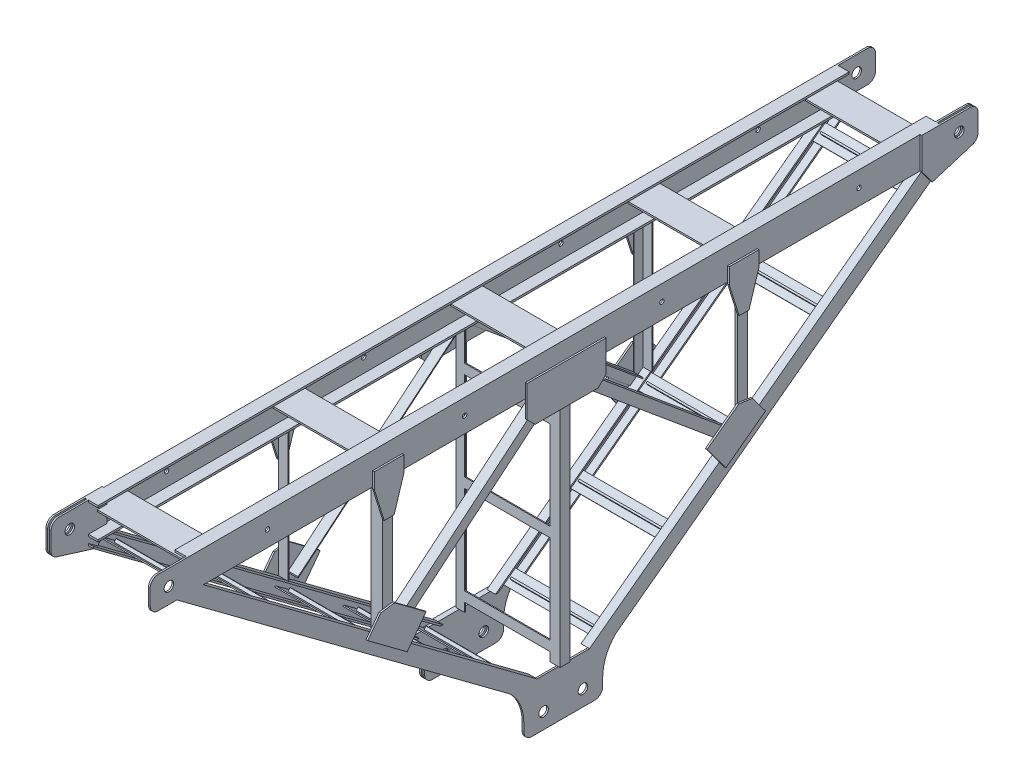
SolidWorks part; units mm, degrees
ref_plane "前视基准面" through (0, 0, 0) normal (0, 0, 1) x (1, 0, 0)
ref_plane "上视基准面" through (0, 0, 0) normal (0, 1, 0) x (1, 0, 0)
ref_plane "右视基准面" through (0, 0, 0) normal (1, 0, 0) x (0, 0, -1)
sketch "草图2" plane through (0, 0, 0) normal (0, 0, 1) x (1, 0, 0)
  line L0 (0, 0) -> (0, 160)
  line L1 (0, 160) -> (65, 160)
  line L2 (65, 160) -> (65, 150)
  line L3 (65, 150) -> (8.5, 150)
  line L4 (8.5, 150) -> (8.5, 10)
  line L5 (8.5, 10) -> (65, 10)
  line L6 (65, 10) -> (65, 0)
  line L7 (65, 0) -> (0, 0)
  line L8 (455, 160) -> (520, 160)
  line L9 (520, 160) -> (520, 0)
  line L10 (520, 0) -> (455, 0)
  line L11 (455, 0) -> (455, 10)
  line L12 (455, 10) -> (511.5, 10)
  line L13 (511.5, 10) -> (511.5, 150)
  line L14 (511.5, 150) -> (455, 150)
  line L15 (455, 150) -> (455, 160)
  dimension "D1" = 160
  dimension "D2" = 10
  dimension "D3" = 8.5
  dimension "D4" = 65
  dimension "D5" = 520
extrude "拉伸1" add sketch "草图2" along normal blind 4190
sketch "草图7" plane through (520, 0, 0) normal (1, 0, 0) x (0, 0, -1)
  line L1 (-2295, -1260) -> (-1895, -1260)
  line L2 (-2295, -1260) -> (-2295, -1500)
  line L3 (-2295, -1500) -> (-1895, -1500)
  line L4 (-1895, -1260) -> (-1895, -1500)
  line L5 (-4190, 160) -> (0, 160) construction
  line L6 (-2095, 160) -> (-2095, -1500) construction
  dimension "D1" = 240
  dimension "D2" = 400
  dimension "D4" = 1660
extrude "拉伸4" add sketch "草图7" against normal blind 520 separate body
sketch "草图8" plane through (0, -1260, 0) normal (0, 1, 0) x (1, 0, 0)
  line L0 (0, -2295) -> (520, -2295) construction
  line L1 (511.5, -2295) -> (8.5, -2295)
  line L2 (511.5, -2295) -> (511.5, -1895)
  line L3 (511.5, -1895) -> (8.5, -1895)
  line L4 (8.5, -2295) -> (8.5, -1895)
  line L5 (0, -1895) -> (520, -1895) construction
  line L6 (0, -1895) -> (0, -2295) construction
  line L7 (520, -1895) -> (520, -2295) construction
  dimension "D1" = 8.5
  dimension "D2" = 8.5
extrude "拉伸5" cut sketch "草图8" against normal through all
sketch "草图9" plane through (520, 0, 0) normal (1, 0, 0) x (0, 0, -1)
  line L0 (-2295, -1500) -> (-1895, -1500) construction
  circle A0 centre (-2195, -1420) radius 11
  circle A1 centre (-1995, -1420) radius 11
  point P6 (-2095, -1500)
  dimension "D1" = 22
  dimension "D2" = 80
  dimension "D3" = 80
  dimension "D4" = 200
  dimension "D5" = 100
extrude "拉伸6" cut sketch "草图9" against normal through all
sketch "草图13" plane through (520, 0, 0) normal (1, 0, 0) x (0, 0, -1)
  line L0 (-2295, -1260) -> (-4095, 80) construction
  line L1 (-95, 80) -> (-1895, -1260) construction
  line L2 (-1961.9855, -1260) -> (-1895, -1260)
  line L3 (-1895, -1260) -> (-2295, -1260) construction
  line L4 (-1895, -1260) -> (-1895, -1309.867)
  line L5 (-1895, -1500) -> (-1895, -1260) construction
  line L6 (-1895, -1309.867) -> (-135.4772, 0)
  line L7 (-4190, 0) -> (0, 0) construction
  line L8 (-135.4772, 0) -> (-269.4482, 0)
  line L9 (-269.4482, 0) -> (-1961.9855, -1260)
  line L10 (-2228.0145, -1260) -> (-2295, -1260)
  line L11 (-2295, -1260) -> (-2295, -1309.867)
  line L12 (-2295, -1260) -> (-2295, -1500) construction
  line L13 (-2295, -1309.867) -> (-4054.5228, 0)
  line L14 (-4054.5228, 0) -> (-3920.5518, 0)
  line L15 (-3920.5518, 0) -> (-2228.0145, -1260)
  line L16 (-4190, 160) -> (0, 160) construction
  line L17 (-4190, 0) -> (-4190, 160) construction
  line L18 (0, 0) -> (0, 160) construction
  dimension "D1" = 80
  dimension "D2" = 40
  dimension "D3" = 80
  dimension "D4" = 40
  dimension "D5" = 80
  dimension "D6" = 95
  dimension "D7" = 95
  dimension "D8" = 80
extrude "拉伸8" add sketch "草图13" against normal blind 43 separate body
sketch "草图14" plane through (477, 0, 0) normal (-1, 0, 0) x (0, 0, 1)
  line L0 (3933.9489, 0) -> (4041.1257, 0)
  line L1 (3920.5518, 0) -> (4054.5228, 0) construction
  line L2 (4041.1257, 0) -> (2295, -1299.8936)
  line L3 (2295, -1309.867) -> (2295, -1260) construction
  line L4 (2295, -1299.8936) -> (2295, -1260)
  line L5 (2295, -1260) -> (2241.4116, -1260)
  line L6 (2295, -1260) -> (2228.0145, -1260) construction
  line L7 (2241.4116, -1260) -> (3933.9489, 0)
  line L8 (4054.5228, 0) -> (2295, -1309.867) construction
  line L9 (2228.0145, -1260) -> (3920.5518, 0) construction
  line L10 (148.8743, 0) -> (256.0511, 0)
  line L11 (135.4772, 0) -> (269.4482, 0) construction
  line L12 (256.0511, 0) -> (1948.5884, -1260)
  line L13 (1961.9855, -1260) -> (1895, -1260) construction
  line L14 (1948.5884, -1260) -> (1895, -1260)
  line L15 (1895, -1260) -> (1895, -1299.8936)
  line L16 (1895, -1260) -> (1895, -1309.867) construction
  line L17 (1895, -1299.8936) -> (148.8743, 0)
  line L18 (1895, -1309.867) -> (135.4772, 0) construction
  line L19 (269.4482, 0) -> (1961.9855, -1260) construction
  dimension "D1" = 8
  dimension "D2" = 8
  dimension "D3" = 8
  dimension "D4" = 8
extrude "拉伸9" cut sketch "草图14" against normal blind 38
sketch "草图15" plane through (0, 0, 0) normal (-1, 0, 0) x (0, 0, 1)
  line L0 (4095, 80) -> (2295, -1260) construction
  line L1 (1895, -1500) -> (1895, -1260) construction
  line L2 (1895, -1260) -> (95, 80) construction
  line L3 (1895, -1260) -> (2295, -1260) construction
  line L4 (3920.5518, 0) -> (4054.5228, 0)
  line L5 (4190, 0) -> (0, 0) construction
  line L6 (4190, 0) -> (0, 0) construction
  line L7 (4054.5228, 0) -> (2295, -1309.867)
  line L8 (2295, -1260) -> (2295, -1500) construction
  line L9 (2295, -1309.867) -> (2295, -1260)
  line L10 (2295, -1260) -> (2228.0145, -1260)
  line L11 (2228.0145, -1260) -> (3920.5518, 0)
  line L12 (135.4772, 0) -> (269.4482, 0)
  line L13 (269.4482, 0) -> (1961.9855, -1260)
  line L14 (1961.9855, -1260) -> (1895, -1260)
  line L15 (1895, -1260) -> (1895, -1309.867)
  line L16 (1895, -1309.867) -> (135.4772, 0)
  line L17 (0, 0) -> (0, 160) construction
  line L18 (4190, 0) -> (4190, 160) construction
  line L19 (4190, 160) -> (0, 160) construction
  dimension "D1" = 40
  dimension "D2" = 40
  dimension "D3" = 80
  dimension "D4" = 40
  dimension "D5" = 80
  dimension "D6" = 95
  dimension "D7" = 95
  dimension "D8" = 80
extrude "拉伸10" add sketch "草图15" against normal blind 43 separate body
sketch "草图16" plane through (43, 0, 0) normal (1, 0, 0) x (0, 0, -1)
  line L0 (-3933.9489, 0) -> (-4041.1257, 0)
  line L1 (-4054.5228, 0) -> (-3920.5518, 0) construction
  line L2 (-4041.1257, 0) -> (-2295, -1299.8936)
  line L3 (-2295, -1260) -> (-2295, -1309.867) construction
  line L4 (-2295, -1299.8936) -> (-2295, -1260)
  line L5 (-2295, -1260) -> (-2241.4116, -1260)
  line L6 (-2228.0145, -1260) -> (-2295, -1260) construction
  line L7 (-2241.4116, -1260) -> (-3933.9489, 0)
  line L8 (-256.0511, 0) -> (-148.8743, 0)
  line L9 (-269.4482, 0) -> (-135.4772, 0) construction
  line L10 (-148.8743, 0) -> (-1895, -1299.8936)
  line L11 (-1895, -1309.867) -> (-1895, -1260) construction
  line L12 (-1895, -1299.8936) -> (-1895, -1260)
  line L13 (-1895, -1260) -> (-1948.5884, -1260)
  line L14 (-1895, -1260) -> (-1961.9855, -1260) construction
  line L15 (-1948.5884, -1260) -> (-256.0511, 0)
  line L16 (-135.4772, 0) -> (-1895, -1309.867) construction
  line L17 (-1961.9855, -1260) -> (-269.4482, 0) construction
  line L18 (-2295, -1309.867) -> (-4054.5228, 0) construction
  line L19 (-3920.5518, 0) -> (-2228.0145, -1260) construction
  dimension "D1" = 8
  dimension "D2" = 8
  dimension "D3" = 8
  dimension "D4" = 8
extrude "拉伸11" cut sketch "草图16" against normal blind 38
sketch "草图17" plane through (0, 0, 0) normal (-1, 0, 0) x (0, 0, 1)
  line L0 (4190, 160) -> (0, 160) construction
  line L1 (4190, 0) -> (0, 0) construction
  line L2 (2070, 0) -> (2120, 0)
  line L3 (2070, 0) -> (2070, -1260)
  line L4 (2070, -1260) -> (2120, -1260)
  line L5 (2120, 0) -> (2120, -1260)
  line L6 (1895, -1260) -> (2295, -1260) construction
  line L7 (2970, 0) -> (2970, -707.633)
  line L8 (3920.5518, 0) -> (2228.0145, -1260) construction
  line L9 (2970, -707.633) -> (3020, -670.4108)
  line L10 (3020, -670.4108) -> (3020, 0)
  line L11 (3020, 0) -> (2970, 0)
  line L12 (1170, 0) -> (1170, -670.4108)
  line L13 (4190, 160) -> (0, 160) construction
  line L14 (1170, -670.4108) -> (1220, -707.633)
  line L16 (1220, -707.633) -> (1220, 0)
  line L17 (1220, 0) -> (1170, 0)
  line L18 (1961.9855, -1260) -> (269.4482, 0) construction
  point P6 (2095, 160)
  point P22 (2095, 160)
  point P26 (2095, 160)
  dimension "D2" = 875
  dimension "D4" = 875
  dimension "D1" = 50
  dimension "D3" = 50
  dimension "D5" = 50
  dimension "D6" = 25
extrude "拉伸12" add sketch "草图17" against normal blind 528.5 separate body
sketch "草图18" plane through (0, -1260, 0) normal (0, -1, 0) x (1, 0, 0)
  line L0 (5, 2115) -> (43, 2115)
  line L1 (43, 2115) -> (43, 2120)
  line L2 (528.5, 2120) -> (0, 2120) construction
  line L3 (43, 2120) -> (477, 2120)
  line L4 (477, 2120) -> (477, 2115)
  line L5 (477, 2115) -> (515, 2115)
  line L6 (515, 2115) -> (515, 2070)
  line L9 (528.5, 2070) -> (0, 2070) construction
  line L10 (515, 2070) -> (5, 2070)
  line L14 (5, 2070) -> (5, 2115)
  line L15 (0, 2295) -> (0, 1895) construction
  line L16 (520, 2295) -> (520, 1895) construction
  dimension "D1" = 5
  dimension "D2" = 5
  dimension "D3" = 5
  dimension "D4" = 43
extrude "拉伸13" cut sketch "草图18" against normal blind 1260
sketch "草图22" plane through (0, 0, 3020) normal (0, 0, 1) x (1, 0, 0)
  line L0 (528.5, 0) -> (0, 0) construction
  line L1 (65, 0) -> (455, 0)
  line L2 (65, 0) -> (65, -1000)
  line L3 (65, -1000) -> (455, -1000)
  line L4 (455, 0) -> (455, -1000)
  line L6 (520, 0) -> (520, -1309.867) construction
  line L7 (0, -1309.867) -> (0, 0) construction
  dimension "D1" = 65
  dimension "D2" = 65
  dimension "D3" = 1000
extrude "拉伸14" cut sketch "草图22" against normal through all
sketch "草图23" plane through (455, 0, 0) normal (-1, 0, 0) x (0, 0, 1)
  line L1 (1170, 0) -> (1220, 0)
  line L2 (1170, 0) -> (1170, -707.633)
  line L3 (1170, -707.633) -> (1220, -707.633)
  line L4 (1220, 0) -> (1220, -707.633)
  line L5 (3020, 0) -> (2970, 0)
  line L6 (3020, 0) -> (3020, -707.633)
  line L7 (3020, -707.633) -> (2970, -707.633)
  line L8 (2970, 0) -> (2970, -707.633)
extrude "拉伸15" cut sketch "草图23" against normal blind 15
sketch "草图25" plane through (65, 0, 0) normal (1, 0, 0) x (0, 0, -1)
  line L1 (-2970, -707.633) -> (-3020, -707.633)
  line L2 (-2970, -707.633) -> (-2970, 0)
  line L3 (-2970, 0) -> (-3020, 0)
  line L4 (-3020, -707.633) -> (-3020, 0)
  line L5 (-1220, -707.633) -> (-1170, -707.633)
  line L6 (-1220, -707.633) -> (-1220, 0)
  line L7 (-1220, 0) -> (-1170, 0)
  line L8 (-1170, -707.633) -> (-1170, 0)
extrude "拉伸16" cut sketch "草图25" against normal blind 15
sketch "草图26" plane through (50, 0, 0) normal (1, 0, 0) x (0, 0, -1)
  line L0 (-3015, 0) -> (-2970, 0)
  line L1 (-2970, 0) -> (-3020, 0) construction
  line L2 (-2970, 0) -> (-2970, -707.633)
  line L3 (-2970, -707.633) -> (-3015, -674.133)
  line L4 (-2970, -707.633) -> (-3020, -670.4108) construction
  line L5 (-3015, -674.133) -> (-3015, 0)
  line L6 (-1175, 0) -> (-1220, 0)
  line L7 (-1170, 0) -> (-1220, 0) construction
  line L8 (-1220, 0) -> (-1220, -707.633)
  line L9 (-1220, -707.633) -> (-1175, -674.133)
  line L10 (-1220, -707.633) -> (-1170, -670.4108) construction
  line L11 (-1175, -674.133) -> (-1175, 0)
  line L12 (-1170, -670.4108) -> (-1170, 0) construction
  line L13 (-3020, 0) -> (-3020, -670.4108) construction
  dimension "D1" = 5
  dimension "D2" = 5
extrude "拉伸17" cut sketch "草图26" against normal blind 45
sketch "草图27" plane through (470, 0, 0) normal (-1, 0, 0) x (0, 0, 1)
  line L0 (3015, 0) -> (2970, 0)
  line L1 (3020, 0) -> (2970, 0) construction
  line L2 (2970, 0) -> (2970, -707.633)
  line L3 (2970, -707.633) -> (3015, -674.133)
  line L4 (2970, -707.633) -> (3020, -670.4108) construction
  line L5 (3015, -674.133) -> (3015, 0)
  line L6 (1175, 0) -> (1220, 0)
  line L7 (1220, 0) -> (1170, 0) construction
  line L8 (1220, 0) -> (1220, -707.633)
  line L9 (1220, -707.633) -> (1175, -674.133)
  line L10 (1220, -707.633) -> (1170, -670.4108) construction
  line L11 (1175, -674.133) -> (1175, 0)
  line L12 (3020, -670.4108) -> (3020, 0) construction
  line L13 (1170, 0) -> (1170, -670.4108) construction
  dimension "D1" = 5
  dimension "D2" = 5
extrude "拉伸18" cut sketch "草图27" against normal blind 45
sketch "草图28" plane through (0, 0, 0) normal (-1, 0, 0) x (0, 0, 1)
  line L0 (2070, 0) -> (1220, -707.633) construction
  line L1 (2970, -707.633) -> (2120, 0) construction
  line L2 (2120, -32.5295) -> (2120, 0)
  line L3 (2120, -1260) -> (2120, 0) construction
  line L4 (2120, 0) -> (2159.0741, 0)
  line L5 (4190, 0) -> (0, 0) construction
  line L6 (2159.0741, 0) -> (2970, -675.1035)
  line L7 (2970, 0) -> (2970, -707.633) construction
  line L8 (2970, -675.1035) -> (2970, -707.633)
  line L9 (2970, -707.633) -> (2949.3719, -722.9895)
  line L10 (3920.5518, 0) -> (2228.0145, -1260) construction
  line L11 (2949.3719, -722.9895) -> (2120, -32.5295)
  line L12 (2030.9259, 0) -> (2070, 0)
  line L13 (2070, 0) -> (2070, -32.5295)
  line L14 (2070, 0) -> (2070, -1260) construction
  line L15 (2070, -32.5295) -> (1240.6281, -722.9895)
  line L16 (1961.9855, -1260) -> (269.4482, 0) construction
  line L17 (1240.6281, -722.9895) -> (1220, -707.633)
  line L18 (1220, -707.633) -> (1220, -675.1035)
  line L19 (1220, -707.633) -> (1220, 0) construction
  line L20 (1220, -675.1035) -> (2030.9259, 0)
  dimension "D1" = 25
  dimension "D2" = 50
  dimension "D3" = 25
  dimension "D4" = 50
extrude "拉伸19" add sketch "草图28" against normal blind 50
sketch "草图29" plane through (50, 0, 0) normal (1, 0, 0) x (0, 0, -1)
  line L0 (-2038.7408, 0) -> (-2070, 0)
  line L1 (-2070, 0) -> (-2030.9259, 0) construction
  line L2 (-2070, 0) -> (-2070, -32.5295)
  line L3 (-2070, -32.5295) -> (-1240.6281, -722.9895)
  line L4 (-1240.6281, -722.9895) -> (-1220, -707.633)
  line L5 (-1220, -707.633) -> (-1220, -681.6094)
  line L6 (-1220, -675.1035) -> (-1220, -707.633) construction
  line L7 (-1220, -681.6094) -> (-2038.7408, 0)
  line L8 (-2030.9259, 0) -> (-1220, -675.1035) construction
  line L9 (-2151.2592, 0) -> (-2120, 0)
  line L10 (-2159.0741, 0) -> (-2120, 0) construction
  line L11 (-2120, 0) -> (-2120, -32.5295)
  line L12 (-2120, -32.5295) -> (-2949.3719, -722.9895)
  line L13 (-2949.3719, -722.9895) -> (-2970, -707.633)
  line L14 (-2970, -707.633) -> (-2970, -681.6094)
  line L15 (-2970, -707.633) -> (-2970, -675.1035) construction
  line L16 (-2970, -681.6094) -> (-2151.2592, 0)
  line L17 (-2970, -675.1035) -> (-2159.0741, 0) construction
  dimension "D1" = 5
  dimension "D2" = 5
extrude "拉伸20" cut sketch "草图29" against normal blind 45
sketch "草图30" plane through (520, 0, 0) normal (1, 0, 0) x (0, 0, -1)
  line L0 (-2070, 0) -> (-1220, -707.633) construction
  line L1 (-1240.6281, -722.9895) -> (-1175, -674.133) construction
  line L2 (-1220, -707.633) -> (-1220, 0) construction
  line L3 (-2120, 0) -> (-2970, -707.633) construction
  line L4 (-2070, 0) -> (-2030.9259, 0)
  line L5 (-4190, 0) -> (0, 0) construction
  line L6 (-2030.9259, 0) -> (-1220, -675.1035)
  line L7 (-1220, -675.1035) -> (-1220, -707.633)
  line L8 (-1220, -707.633) -> (-1240.6281, -722.9895)
  line L9 (-269.4482, 0) -> (-1961.9855, -1260) construction
  line L10 (-1240.6281, -722.9895) -> (-2070, -32.5295)
  line L11 (-2070, 0) -> (-2070, -1260) construction
  line L12 (-2070, -32.5295) -> (-2070, 0)
  line L13 (-2120, 0) -> (-2120, -32.5295)
  line L14 (-2120, -1260) -> (-2120, 0) construction
  line L15 (-2120, -32.5295) -> (-2949.3719, -722.9895)
  line L16 (-2228.0145, -1260) -> (-3920.5518, 0) construction
  line L17 (-2949.3719, -722.9895) -> (-2970, -707.633)
  line L18 (-2970, -707.633) -> (-2970, -675.1035)
  line L19 (-2970, 0) -> (-2970, -707.633) construction
  line L20 (-2970, -675.1035) -> (-2159.0741, 0)
  line L21 (-2159.0741, 0) -> (-2120, 0)
  dimension "D1" = 50
  dimension "D2" = 25
  dimension "D3" = 25
  dimension "D4" = 50
extrude "拉伸21" add sketch "草图30" against normal blind 50
sketch "草图31" plane through (470, 0, 0) normal (-1, 0, 0) x (0, 0, 1)
  line L0 (2120, 0) -> (2151.2592, 0)
  line L1 (2120, 0) -> (2159.0741, 0) construction
  line L2 (2151.2592, 0) -> (2970, -681.6094)
  line L3 (2970, -675.1035) -> (2970, -707.633) construction
  line L4 (2970, -681.6094) -> (2970, -707.633)
  line L5 (2970, -707.633) -> (2949.3719, -722.9895)
  line L6 (2949.3719, -722.9895) -> (2120, -32.5295)
  line L7 (2120, -32.5295) -> (2120, 0)
  line L8 (2038.7408, 0) -> (2070, 0)
  line L9 (2030.9259, 0) -> (2070, 0) construction
  line L10 (2070, 0) -> (2070, -32.5295)
  line L11 (2070, -32.5295) -> (1240.6281, -722.9895)
  line L12 (1240.6281, -722.9895) -> (1220, -707.633)
  line L13 (1220, -707.633) -> (1220, -681.6094)
  line L14 (1220, -707.633) -> (1220, -675.1035) construction
  line L15 (1220, -681.6094) -> (2038.7408, 0)
  line L16 (1220, -675.1035) -> (2030.9259, 0) construction
  line L17 (2159.0741, 0) -> (2970, -675.1035) construction
  dimension "D1" = 5
  dimension "D2" = 5
extrude "拉伸22" cut sketch "草图31" against normal blind 45
sketch "草图32" plane through (0, 0, 0) normal (-1, 0, 0) x (0, 0, 1)
  line L0 (0, 80) -> (4190, 80) construction
  line L1 (1120, 80) -> (1270, 80)
  line L2 (1895, 80) -> (2295, 80)
  line L3 (1895, 80) -> (1895, -120)
  line L4 (1895, -120) -> (2295, -120)
  line L5 (2295, 80) -> (2295, -120)
  line L6 (1270, 80) -> (1270, 0)
  line L7 (2030.9259, 0) -> (1220, 0) construction
  line L8 (1270, 0) -> (1220, -160)
  line L9 (1220, -675.1035) -> (1220, 0) construction
  line L10 (1220, -160) -> (1170, -160)
  line L11 (1170, 0) -> (1170, -670.4108) construction
  line L12 (1170, -160) -> (1120, 0)
  line L13 (1170, 0) -> (269.4482, 0) construction
  line L14 (1120, 0) -> (1120, 80)
  line L15 (2920, 80) -> (3070, 80)
  line L16 (3070, 80) -> (3070, 0)
  line L17 (3920.5518, 0) -> (3020, 0) construction
  line L18 (3070, 0) -> (3020, -160)
  line L19 (3020, -670.4108) -> (3020, 0) construction
  line L20 (3020, -160) -> (2970, -160)
  line L21 (2970, 0) -> (2970, -675.1035) construction
  line L22 (2970, -160) -> (2920, 0)
  line L23 (2970, 0) -> (2159.0741, 0) construction
  line L24 (2920, 0) -> (2920, 80)
  line L25 (2807.6858, -666.3992) -> (3008.2193, -517.1132)
  line L26 (2807.6858, -666.3992) -> (2903.2289, -794.7406)
  line L27 (3008.2193, -517.1132) -> (3103.7624, -645.4546)
  line L28 (2903.2289, -794.7406) -> (3103.7624, -645.4546)
  line L29 (2295, -1309.867) -> (4054.5228, 0) construction
  line L30 (2970, -675.1035) -> (3033.3528, -760.2043) construction
  line L31 (1181.7807, -517.1132) -> (1382.3142, -666.3992)
  line L32 (1181.7807, -517.1132) -> (1086.2376, -645.4546)
  line L33 (1382.3142, -666.3992) -> (1286.7711, -794.7406)
  line L34 (1086.2376, -645.4546) -> (1286.7711, -794.7406)
  line L35 (4190, 160) -> (0, 160) construction
  line L36 (0, 0) -> (0, 160) construction
  line L37 (4190, 0) -> (4190, 160) construction
  line L38 (135.4772, 0) -> (1895, -1309.867) construction
  line L39 (1220, -675.1035) -> (1156.6472, -760.2043) construction
  point P8 (2095, 160)
  dimension "D3" = 200
  dimension "D1" = 400
  dimension "D2" = 200
  dimension "D4" = 150
  dimension "D5" = 240
  dimension "D6" = 150
  dimension "D7" = 240
  dimension "D8" = 250
  dimension "D9" = 160
  dimension "D10" = 50
  dimension "D11" = 125
  dimension "D12" = 250
  dimension "D13" = 160
  dimension "D14" = 50
  dimension "D15" = 125
extrude "拉伸23" add sketch "草图32" along normal blind 8.5
pattern_linear "阵列(线性)7" count 2 spacing 537 along (1, 0, 0) of "拉伸23"
sketch "草图33" plane through (0, 0, 0) normal (-1, 0, 0) x (0, 0, 1)
  line L0 (195, 86.5) -> (270.75, 86.5)
  line L1 (195, 95) -> (355, 95)
  line L2 (195, 95) -> (195, 86.5)
  line L3 (279.25, 86.5) -> (355, 86.5)
  line L4 (355, 95) -> (355, 86.5)
  line L5 (95, 80) -> (4190, 80) construction
  line L6 (270.75, 86.5) -> (270.75, 46.5)
  line L7 (270.75, 46.5) -> (279.25, 46.5)
  line L8 (279.25, 86.5) -> (279.25, 46.5)
  line L9 (0, 160) -> (0, 0) construction
  line L11 (4190, 0) -> (4190, 160) construction
  dimension "D1" = 160
  dimension "D2" = 8.5
  dimension "D3" = 40
  dimension "D4" = 15
  dimension "D5" = 100
  dimension "D6" = 95
extrude "拉伸24" add sketch "草图33" against normal blind 520
pattern_linear "阵列(线性)8" count 5 spacing 900 along (0, 0, 1) of "拉伸24"
sketch "草图34" plane through (0, 0, 0) normal (-1, 0, 0) x (0, 0, 1)
  line L0 (3033.3528, -760.2043) -> (2970, -675.1035) construction
  line L1 (2295, -1309.867) -> (4054.5228, 0) construction
  line L2 (2975.8889, -749.9994) -> (2978.8746, -754.0101)
  line L3 (2975.8889, -749.9994) -> (3040.0596, -702.2279)
  line L4 (2978.8746, -754.0101) -> (3043.0453, -706.2385)
  line L5 (3040.0596, -702.2279) -> (3043.0453, -706.2385)
  dimension "D1" = 5
  dimension "D2" = 80
  dimension "D3" = 40
  dimension "D4" = 37.5
extrude "拉伸25" add sketch "草图34" against normal blind 520
sketch "草图35" plane through (0, -1907.9835, 1420.3877) normal (0, 0.8021, -0.5971) x (1, 0, 0)
  line L1 (40, -1973.2037) -> (488.5, -1973.2037)
  line L2 (40, -1973.2037) -> (40, -1981.7037)
  line L3 (40, -1981.7037) -> (488.5, -1981.7037)
  line L4 (488.5, -1973.2037) -> (488.5, -1981.7037)
  line L7 (0, -2056.5567) -> (0, -1954.1491) construction
  line L8 (528.5, -2056.5567) -> (528.5, -1854.2037) construction
  line L9 (515, -2019.2037) -> (5, -2019.2037) construction
  dimension "D1" = 40
  dimension "D2" = 40
  dimension "D3" = 8.5
  dimension "D4" = 37.5
extrude "拉伸26" add sketch "草图35" along normal blind 15
pattern_linear "阵列(线性)9" count 3 spacing 430 along (0, -0.5971, -0.8021) of "拉伸25", "拉伸26"
pattern_linear "阵列(线性)10" count 3 spacing 550 along (0, 0.5971, 0.8021) of "拉伸25", "拉伸26"
ref_plane "基准面2" through (0, 0, 2095) normal (0, 0, 1) x (1, 0, 0)
mirror "镜向13" about plane through (0, 0, 2095) normal (0, 0, 1) of "阵列(线性)10", "阵列(线性)9", "拉伸26", "拉伸25"
sketch "草图36" plane through (520, 0, 0) normal (1, 0, 0) x (0, 0, -1)
  line L0 (-2120, -1260) -> (-2120, -120) construction
  line L1 (-2120, -665) -> (-2070, -665)
  line L2 (-2120, -665) -> (-2120, -715)
  line L3 (-2120, -715) -> (-2070, -715)
  line L4 (-2070, -665) -> (-2070, -715)
  line L5 (-2070, -120) -> (-2070, -1260) construction
  point P8 (-2070, -690)
  dimension "D1" = 50
  dimension "D2" = 25
extrude "拉伸27" add sketch "草图36" against normal blind 520
sketch "草图37" plane through (0, -665, 0) normal (0, 1, 0) x (1, 0, 0)
  line L1 (5, -2115) -> (515, -2115)
  line L2 (5, -2115) -> (5, -2070)
  line L3 (5, -2070) -> (515, -2070)
  line L4 (515, -2115) -> (515, -2070)
extrude "拉伸28" cut sketch "草图37" against normal blind 45
pattern_linear "阵列(线性)11" count 2 spacing 500 along (0, 1, 0) of "拉伸27", "拉伸28"
pattern_linear "阵列(线性)13" count 2 spacing 500 along (0, -1, 0) of "拉伸27", "拉伸28"
sketch "草图38" plane through (0, 160, 0) normal (0, 1, 0) x (1, 0, 0)
  line L0 (520, -4190) -> (520, 0) construction
  line L1 (8.5, 0) -> (511.5, 0)
  line L2 (8.5, 0) -> (8.5, -190)
  line L3 (8.5, -190) -> (511.5, -190)
  line L4 (511.5, 0) -> (511.5, -190)
  line L5 (0, -4190) -> (0, 0) construction
  line L6 (65, 0) -> (0, 0) construction
  line L8 (8.5, -4000) -> (511.5, -4000)
  line L9 (8.5, -4000) -> (8.5, -4190)
  line L10 (8.5, -4190) -> (511.5, -4190)
  line L11 (511.5, -4000) -> (511.5, -4190)
  dimension "D1" = 8.5
  dimension "D2" = 8.5
  dimension "D3" = 190
  dimension "D4" = 8.5
  dimension "D5" = 190
extrude "拉伸29" cut sketch "草图38" against normal through all
sketch "草图39" plane through (520, 0, 0) normal (1, 0, 0) x (0, 0, -1)
  line L0 (-285, 160) -> (0, 160)
  line L1 (-4190, 160) -> (0, 160) construction
  line L2 (0, 160) -> (0, 0)
  line L3 (0, 0) -> (-231.683, -71.6199)
  line L4 (-1895, -1309.867) -> (-135.4772, 0) construction
  line L5 (-285, 160) -> (-285, 0)
  line L6 (-1170, 0) -> (-269.4482, 0) construction
  line L7 (-285, 0) -> (-231.683, -71.6199)
  line L8 (-269.4482, 0) -> (-1170, -670.4108) construction
  dimension "D1" = 285
extrude "拉伸30" add sketch "草图39" along normal blind 8.5
pattern_linear "阵列(线性)14" count 2 spacing 17 along (-1, 0, 0) of "拉伸30"
sketch "草图41" plane through (0, 160, 0) normal (0, 1, 0) x (1, 0, 0)
  line L0 (528.5, 0) -> (503, 0) construction
  line L1 (511.5, 0) -> (520, 0)
  line L2 (511.5, 0) -> (511.5, -190)
  line L3 (511.5, -190) -> (520, -190)
  line L4 (520, 0) -> (520, -190)
  line L5 (528.5, 0) -> (528.5, -285) construction
  line L6 (503, 0) -> (503, -190) construction
  dimension "D1" = 190
  dimension "D2" = 8.5
  dimension "D3" = 8.5
extrude "拉伸31" cut sketch "草图41" against normal through all
sketch "草图42" plane through (528.5, 0, 0) normal (1, 0, 0) x (0, 0, -1)
  line L0 (0, 160) -> (-285, 160) construction
  line L1 (0, 0) -> (0, 160) construction
  circle A0 centre (-95, 80) radius 24.25
  dimension "D1" = 48.5
  dimension "D2" = 80
  dimension "D3" = 95
extrude "拉伸32" cut sketch "草图42" against normal through all
sketch "草图43" plane through (0, 0, 0) normal (-1, 0, 0) x (0, 0, 1)
  line L1 (4190, 160) -> (0, 160) construction
  line L2 (3905, 160) -> (3905, 0)
  line L3 (3920.5518, 0) -> (3070, 0) construction
  line L4 (3905, 0) -> (3958.317, -71.6199)
  line L5 (2295, -1309.867) -> (4054.5228, 0) construction
  line L6 (3958.317, -71.6199) -> (4190, 0)
  line L7 (4190, 160) -> (4190, 0) construction
  line L8 (4190, 0) -> (4190, 160)
  line L9 (3905, 160) -> (4190, 160)
  line L10 (3920.5518, 0) -> (3085.848, -621.3906) construction
  dimension "D1" = 285
extrude "拉伸33" add sketch "草图43" along normal blind 8.5
pattern_linear "阵列(线性)15" count 2 spacing 17 along (1, 0, 0) of "拉伸33"
sketch "草图44" plane through (0, 160, 0) normal (0, 1, 0) x (1, 0, 0)
  line L0 (17, -4190) -> (-8.5, -4190) construction
  line L1 (8.5, -4190) -> (0, -4190)
  line L2 (8.5, -4190) -> (8.5, -4000)
  line L3 (8.5, -4000) -> (0, -4000)
  line L4 (0, -4190) -> (0, -4000)
  line L5 (-8.5, -4190) -> (-8.5, -3905) construction
  line L6 (17, -4190) -> (17, -4000) construction
  dimension "D1" = 190
  dimension "D2" = 8.5
  dimension "D3" = 8.5
extrude "拉伸34" cut sketch "草图44" against normal blind 160
sketch "草图45" plane through (-8.5, 0, 0) normal (-1, 0, 0) x (0, 0, 1)
  line L0 (4190, 160) -> (3905, 160) construction
  line L3 (4190, 0) -> (4190, 160) construction
  circle A0 centre (4095, 80) radius 24.25
  dimension "D1" = 48.5
  dimension "D2" = 80
  dimension "D3" = 95
extrude "拉伸35" cut sketch "草图45" against normal through all
fillet "圆角1" radius 40 12 edges at (4.25, 0, 0) (4.25, 160, 0) (507.25, 0, 0) (524.25, 0, 0) (507.25, 160, 0) (524.25, 160, 0) (-4.25, 0, 4190) (12.75, 0, 4190) (-4.25, 160, 4190) (12.75, 160, 4190) (515.75, 0, 4190) (515.75, 160, 4190)
chamfer "倒角1" distance 50 angle 45 4 edges at (-4.25, -517.1132, 1181.7807) (-4.25, -517.1132, 3008.2193) (532.75, -517.1132, 3008.2193) (532.75, -517.1132, 1181.7807)
sketch "草图47" plane through (0, 0, 0) normal (-1, 0, 0) x (0, 0, 1)
  line L0 (1828.0145, -1260) -> (2361.9855, -1260)
  line L1 (135.4772, 0) -> (1895, -1309.867) construction
  line L2 (2295, -1309.867) -> (3958.317, -71.6199) construction
  line L3 (1895, -1260) -> (2295, -1260) construction
  line L4 (1895, -1420) -> (1895, -1500)
  line L5 (1895, -1500) -> (1895, -1260) construction
  line L6 (1895, -1500) -> (2295, -1500)
  line L7 (2295, -1500) -> (2295, -1420)
  line L8 (2295, -1260) -> (2295, -1500) construction
  arc A0 (2295, -1420) -> (2361.9855, -1260) centre (2519.5789, -1420) cw
  arc A1 (1895, -1420) -> (1828.0145, -1260) centre (1670.4211, -1420) ccw
  dimension "D1" = 80
extrude "拉伸37" add sketch "草图47" along normal blind 8.5
pattern_linear "阵列(线性)16" count 3 spacing 8.5 along (1, 0, 0) of "拉伸37"
sketch "草图48" plane through (0, -1500, 0) normal (0, -1, 0) x (1, 0, 0)
  line L0 (17, 1895) -> (17, 2295) construction
  line L1 (8.5, 2395) -> (0, 2395)
  line L2 (8.5, 2395) -> (8.5, 1795)
  line L3 (8.5, 1795) -> (0, 1795)
  line L4 (0, 2395) -> (0, 1795)
  line L5 (-8.5, 1895) -> (-8.5, 2295) construction
  line L6 (-8.5, 2295) -> (17, 2295) construction
  line L7 (-8.5, 1895) -> (17, 1895) construction
  dimension "D1" = 8.5
  dimension "D2" = 8.5
  dimension "D3" = 100
  dimension "D4" = 100
extrude "拉伸38" cut sketch "草图48" against normal blind 160
sketch "草图49" plane through (520, 0, 0) normal (1, 0, 0) x (0, 0, -1)
  line L0 (-2361.9855, -1260) -> (-1828.0145, -1260)
  line L1 (-4054.5228, 0) -> (-2295, -1309.867) construction
  line L2 (-1895, -1309.867) -> (-231.683, -71.6199) construction
  line L3 (-1895, -1260) -> (-2295, -1260) construction
  line L4 (-2295, -1420) -> (-2295, -1500)
  line L5 (-2295, -1260) -> (-2295, -1500) construction
  line L6 (-2295, -1500) -> (-1895, -1500)
  line L7 (-1895, -1500) -> (-1895, -1420)
  line L8 (-1895, -1500) -> (-1895, -1260) construction
  arc A0 (-1895, -1420) -> (-1828.0145, -1260) centre (-1670.4211, -1420) cw
  arc A1 (-2295, -1420) -> (-2361.9855, -1260) centre (-2519.5789, -1420) ccw
  dimension "D1" = 80
extrude "拉伸39" add sketch "草图49" against normal blind 8.5
fillet "圆角2" radius 40 2 edges at (515.75, -1500, 2295) (515.75, -1500, 1895)
sketch "草图50" plane through (-8.5, 0, 0) normal (-1, 0, 0) x (0, 0, 1)
  line L0 (1935, -1500) -> (2255, -1500) construction
  circle A0 centre (1995, -1420) radius 24.25
  circle A1 centre (2195, -1420) radius 24.25
  point P8 (2095, -1500)
  dimension "D1" = 48.5
  dimension "D2" = 80
  dimension "D3" = 100
  dimension "D4" = 200
  dimension "D5" = 80
extrude "拉伸40" cut sketch "草图50" against normal through all
sketch "草图51" plane through (0, -1260, 0) normal (0, -1, 0) x (1, 0, 0)
  line L0 (511.5, 2120) -> (477, 2120) construction
  line L1 (17, 2620) -> (511.5, 2620)
  line L2 (17, 2620) -> (17, 1620)
  line L3 (17, 1620) -> (511.5, 1620)
  line L4 (511.5, 2620) -> (511.5, 1620)
  line L5 (511.5, 2120) -> (511.5, 2115) construction
  line L6 (17, 2120) -> (17, 2115) construction
  dimension "D1" = 1000
  dimension "D2" = 500
extrude "拉伸41" cut sketch "草图51" along normal through all
chamfer "倒角2" distance 40 angle 45 4 edges at (532.75, -120, 1895) (-4.25, -120, 1895) (-4.25, -120, 2295) (532.75, -120, 2295)
sketch "草图52" plane through (520, 0, 0) normal (1, 0, 0) x (0, 0, -1)
  line L0 (-4150, 160) -> (-285, 160) construction
  circle A0 centre (-3595, 80) radius 11
  circle A1 centre (-4095, 80) radius 24.25 construction
  dimension "D1" = 500
  dimension "D3" = 22
  dimension "D2" = 80
extrude "拉伸42" cut sketch "草图52" against normal through all
pattern_linear "阵列(线性)17" count 4 spacing 1000 along (0, 0, -1) of "拉伸42"
